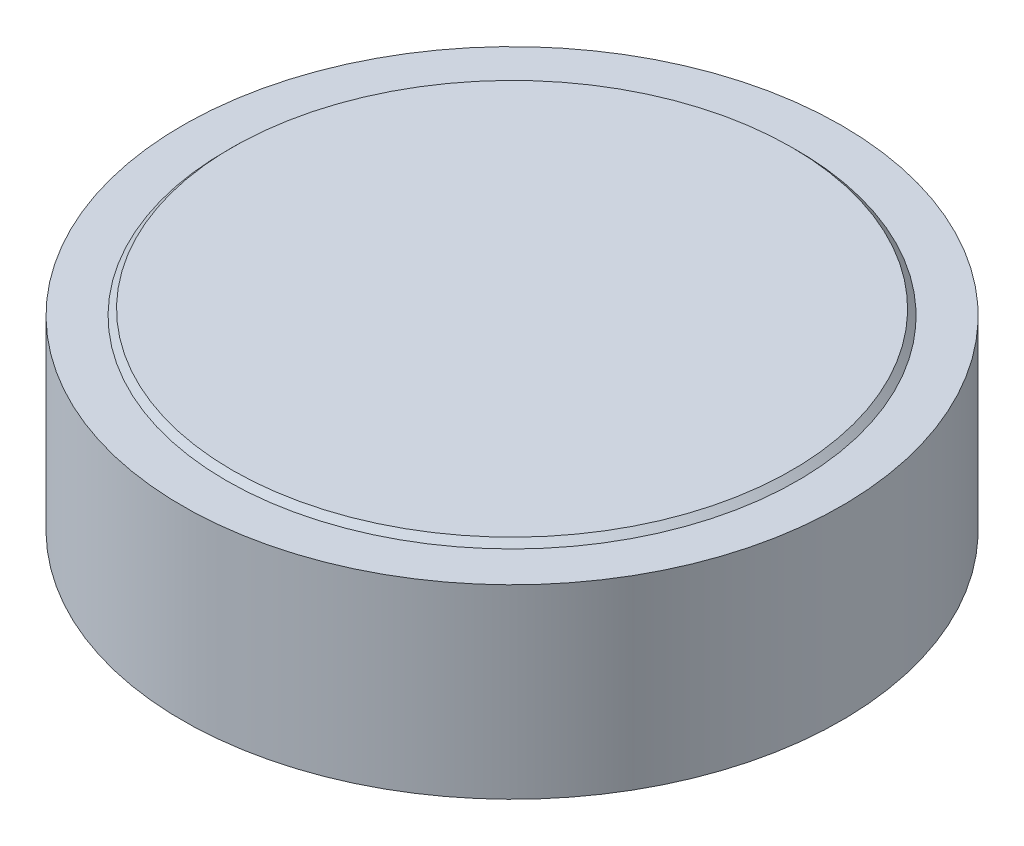
SolidWorks part; units mm, degrees
ref_plane "Front Plane" through (0, 0, 0) normal (0, 0, 1) x (1, 0, 0)
ref_plane "Top Plane" through (0, 0, 0) normal (0, 1, 0) x (1, 0, 0)
ref_plane "Right Plane" through (0, 0, 0) normal (1, 0, 0) x (0, 0, -1)
sketch "Sketch1" plane through (0, 0, 0) normal (0, 1, 0) x (1, 0, 0)
  circle A0 centre (0, 0) radius 5.5
extrude "Boss-Extrude1" add sketch "Sketch1" along normal blind 3.1 contours A0
sketch "Sketch2" plane through (0, 3.1, 0) normal (0, 1, 0) x (1, 0, 0)
  circle A0 centre (0, 0) radius 5.1678
extrude "Boss-Extrude2" add sketch "Sketch2" along normal blind 0.1 contours A0
chamfer "Chamfer1" distance 0.5 angle 45 1 edges at (0, 3.2, 5.1678)
